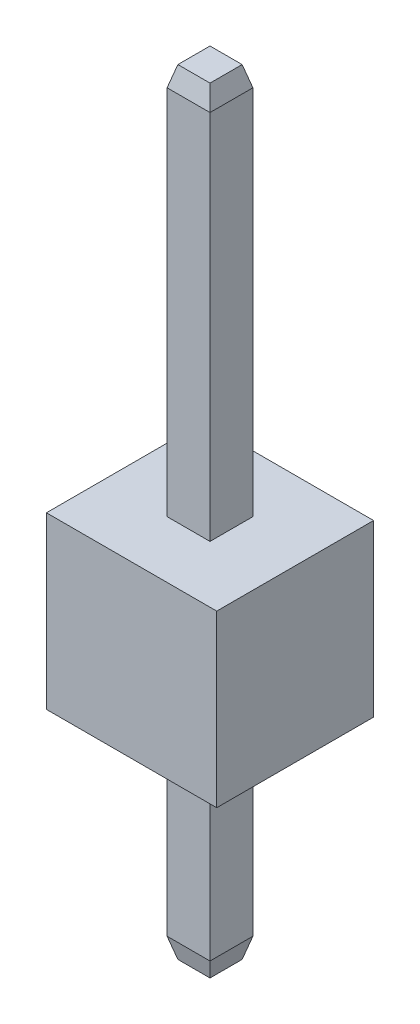
SolidWorks part; units mm, degrees
note: '?' marks a value the reader was unsure of.
ref_plane "Front Plane" through (0, 0, 0) normal (0, 0, 1) x (1, 0, 0)
ref_plane "Top Plane" through (0, 0, 0) normal (0, 1, 0) x (1, 0, 0)
ref_plane "Right Plane" through (0, 0, 0) normal (1, 0, 0) x (0, 0, -1)
sketch "Sketch1" plane through (0, 0, 0) normal (0, 1, 0) x (1, 0, 0)
  line L1 (-0.32, 0.32) -> (0.32, 0.32)
  line L2 (-0.32, 0.32) -> (-0.32, -0.32)
  line L3 (-0.32, -0.32) -> (0.32, -0.32)
  line L4 (0.32, 0.32) -> (0.32, -0.32)
  line L5 (-0.32, 0.32) -> (0.32, -0.32) construction
  line L6 (-0.32, -0.32) -> (0.32, 0.32) construction
  point P0 (0, 0)
  dimension "D1" = 0.64
  dimension "D2" = 0.64
extrude "Boss-Extrude1" add sketch "Sketch1" against normal blind 3.18 and the other way blind 8.38
sketch "Sketch2" plane through (0, 0, 0) normal (0, 1, 0) x (1, 0, 0)
  line L1 (-1.27, 1.17) -> (1.27, 1.17)
  line L2 (-1.27, 1.17) -> (-1.27, -1.17)
  line L3 (-1.27, -1.17) -> (1.27, -1.17)
  line L4 (1.27, 1.17) -> (1.27, -1.17)
  line L5 (-1.27, 1.17) -> (1.27, -1.17) construction
  line L6 (-1.27, -1.17) -> (1.27, 1.17) construction
  point P0 (0, 0)
  dimension "D1" = 1.17
  dimension "D2" = 2.54
extrude "Boss-Extrude2" add sketch "Sketch2" along normal blind 2.54
chamfer "Chamfer1" distance 0.3 angle 15 8 edges at (0, -3.18, -0.32) (-0.32, -3.18, 0) (0, -3.18, 0.32) (0.32, -3.18, 0) (-0.32, 8.38, 0) (0, 8.38, -0.32) (0.32, 8.38, 0) (0, 8.38, 0.32)
ref_axis "Pin axis" through (0, 11.0475, 0) along (0, -1, 0)?
equation "\"D2@Boss-Extrude1\"=\"mating_length\"+\"insulation_height\""
equation "\"mating_length\" = 5.84"
equation "\"insulation_height\" = 2.54"
equation "\"D1@Boss-Extrude2\"=\"insulation_height\""
